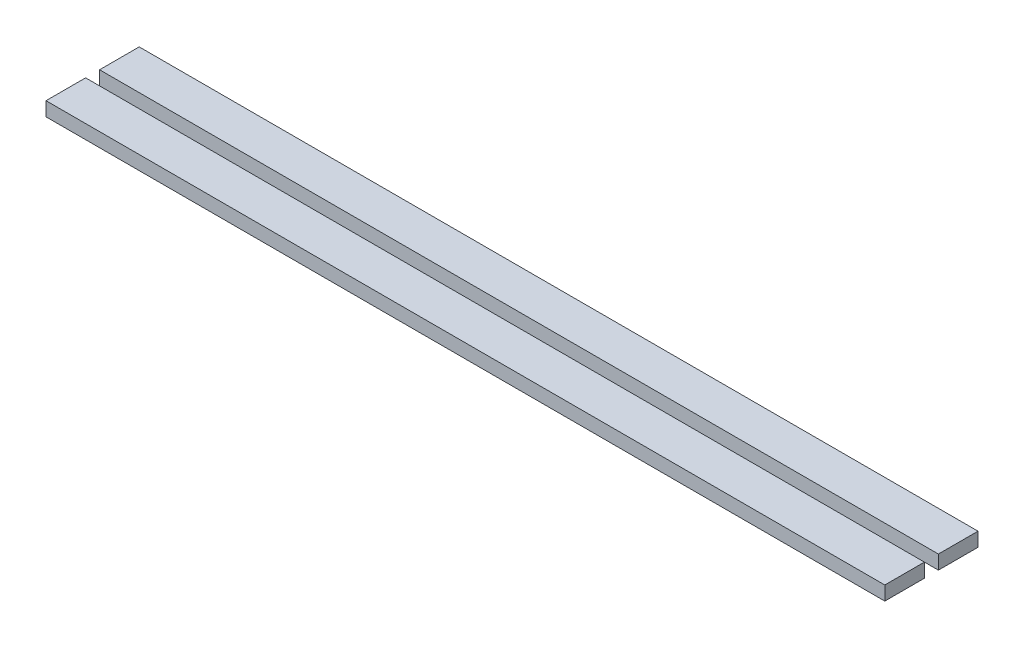
SolidWorks part; units mm, degrees
ref_plane "Front Plane" through (0, 0, 0) normal (0, 0, 1) x (1, 0, 0)
ref_plane "Top Plane" through (0, 0, 0) normal (0, 1, 0) x (1, 0, 0)
ref_plane "Right Plane" through (0, 0, 0) normal (1, 0, 0) x (0, 0, -1)
sketch "Sketch1" plane through (0, 0, 0) normal (0, 1, 0) x (1, 0, 0)
  line L1 (-74.717, 39.9057) -> (105.283, 39.9057)
  line L2 (-74.717, 39.9057) -> (-74.717, 19.9057)
  line L3 (-74.717, 19.9057) -> (105.283, 19.9057)
  line L4 (105.283, 39.9057) -> (105.283, 19.9057)
  dimension "D1" = 180
  dimension "D2" = 20
extrude "Boss-Extrude1" add sketch "Sketch1" along normal blind 3
sketch "Sketch2" plane through (0, 3, 0) normal (0, 1, 0) x (1, 0, 0)
  line L0 (-74.717, 39.9057) -> (-74.717, 19.9057) construction
  line L1 (-74.717, 31.4057) -> (105.283, 31.4057)
  line L2 (-74.717, 31.4057) -> (-74.717, 28.4057)
  line L3 (-74.717, 28.4057) -> (105.283, 28.4057)
  line L4 (105.283, 31.4057) -> (105.283, 28.4057)
  line L5 (105.283, 19.9057) -> (105.283, 39.9057) construction
  line L6 (105.283, 39.9057) -> (-74.717, 39.9057) construction
  dimension "D1" = 3
  dimension "D2" = 8.5
extrude "Cut-Extrude1" cut sketch "Sketch2" against normal through all and the other way blind 10
